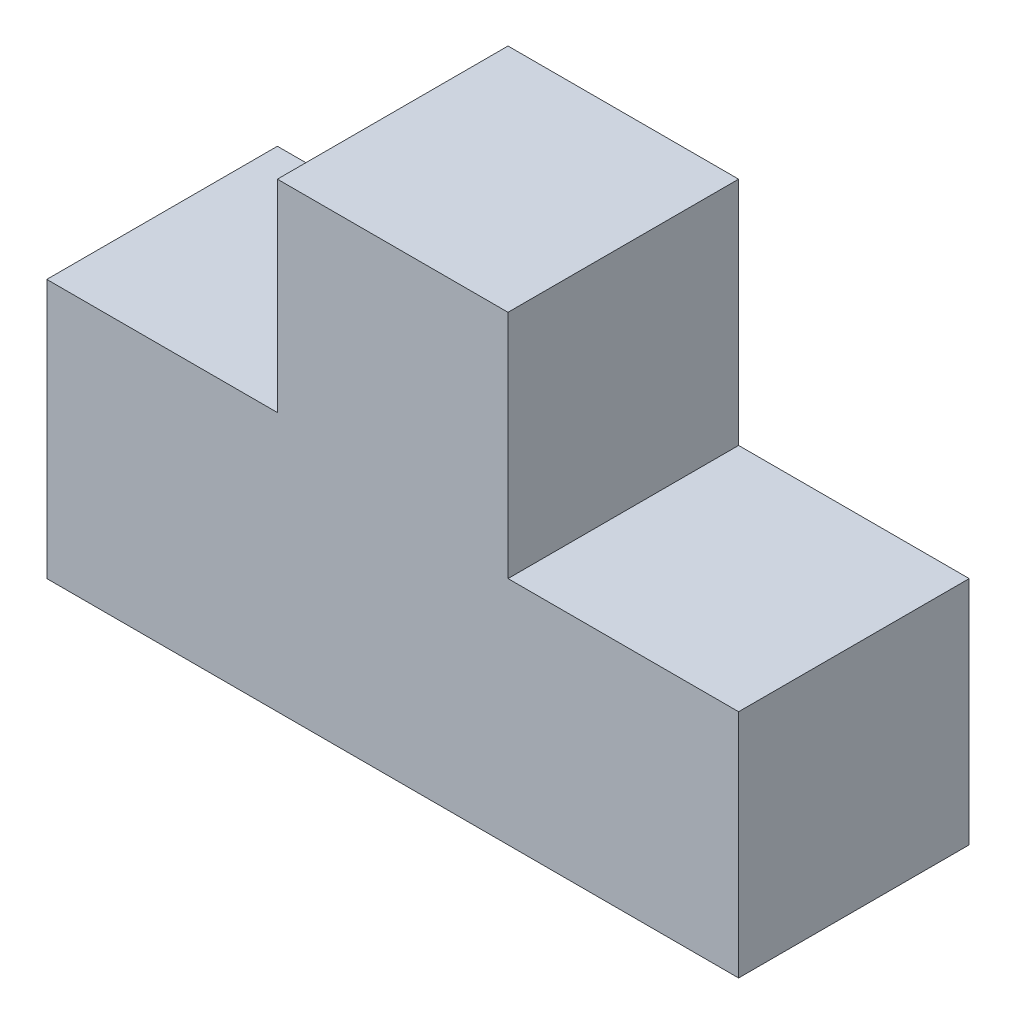
SolidWorks part; units mm, degrees
material "A286 Iron Base Superalloy"
ref_plane "Front Plane" through (0, 0, 0) normal (0, 0, 1) x (1, 0, 0)
ref_plane "Top Plane" through (0, 0, 0) normal (0, 1, 0) x (1, 0, 0)
ref_plane "Right Plane" through (0, 0, 0) normal (1, 0, 0) x (0, 0, -1)
sketch "Sketch1" plane through (0, 0, 0) normal (0, 0, 1) x (1, 0, 0)
  line L0 (0, 0) -> (90, 0)
  line L1 (90, 0) -> (90, 30)
  line L2 (90, 30) -> (60, 30)
  line L3 (60, 30) -> (60, 60)
  line L4 (60, 60) -> (30, 60)
  line L5 (30, 60) -> (30, 33.7072)
  line L6 (30, 33.7072) -> (0, 33.7072)
  line L7 (0, 33.7072) -> (0, 0)
  dimension "D1" = 90
  dimension "D2" = 30
  dimension "D3" = 30
  dimension "D4" = 30
  dimension "D5" = 30
  dimension "D6" = 30
extrude "Boss-Extrude1" add sketch "Sketch1" along normal blind 30
